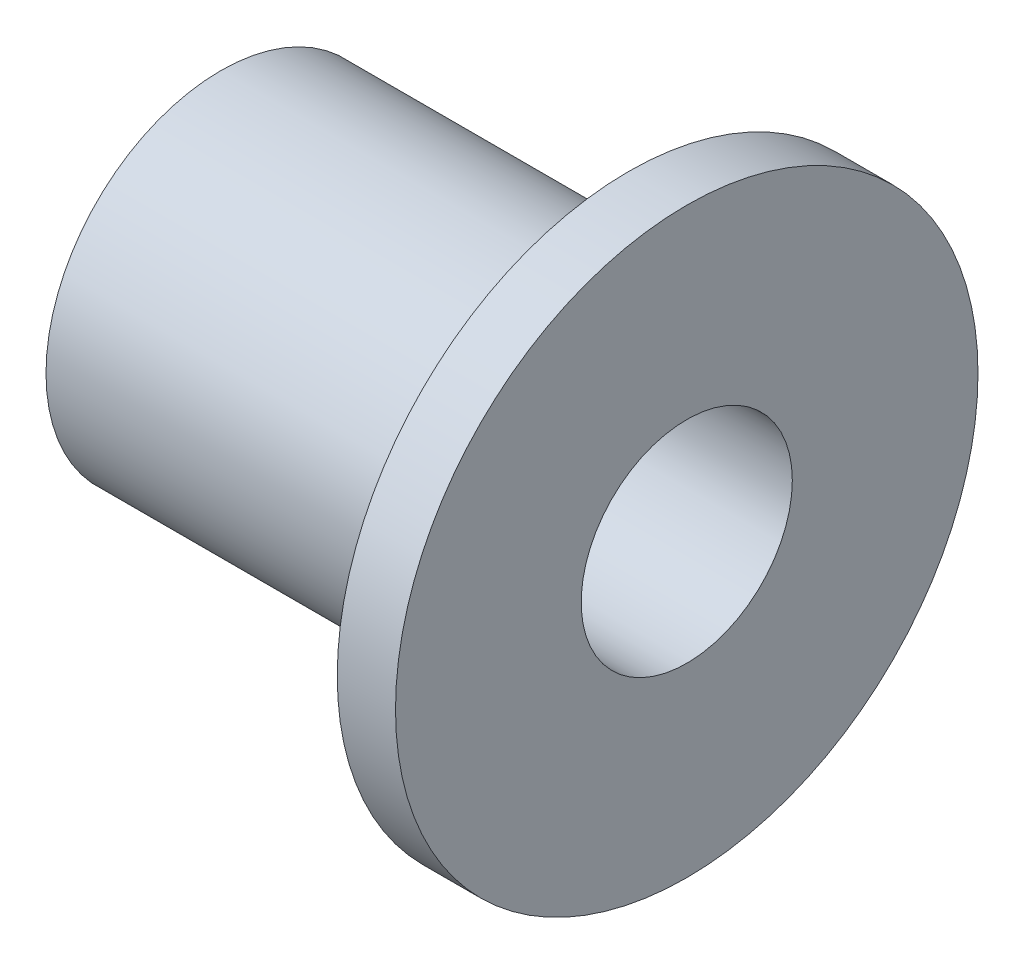
SolidWorks part; units mm, degrees
material "6061 Alloy"
ref_plane "Front Plane" through (0, 0, 0) normal (0, 0, 1) x (1, 0, 0)
ref_plane "Top Plane" through (0, 0, 0) normal (0, 1, 0) x (1, 0, 0)
ref_plane "Right Plane" through (0, 0, 0) normal (1, 0, 0) x (0, 0, -1)
sketch "Sketch1" plane through (0, 0, 0) normal (0, 0, 1) x (1, 0, 0)
  line L0 (0, 9.525) -> (22.225, 9.525)
  line L1 (22.225, 9.525) -> (22.225, 15.875)
  line L2 (22.225, 15.875) -> (25.4, 15.875)
  line L3 (25.4, 15.875) -> (25.4, 0)
  line L4 (25.4, 0) -> (0, 0)
  line L5 (0, 0) -> (0, 9.525)
  line L6 (0, 0) -> (39.6986, 0) construction
  dimension "D1" = 9.525
  dimension "D2" = 22.225
  dimension "D3" = 3.175
  dimension "D4" = 15.875
revolve "Revolve1" add sketch "Sketch1" angle 360 about L6
sketch "Sketch2" plane through (25.4, 0, 0) normal (1, 0, 0) x (0, 0, -1)
  point P0 (0, 0)
hole_wizard "1/2-20 Tapped Hole1" positions "3DSketch1" profile "Sketch3" tap size "1/2-20" standard "Ansi Inch" end condition through all
sketch3d "3DSketch1"
  point P0 (25.4, 0, 0)
sketch "Sketch3" plane through (25.4, 0, 0) normal (0, 1, 0) x (0, 0, -1)
  line L0 (0, 0) -> (0, 25.4)
  line L1 (0, 25.4) -> (5.7544, 25.4)
  line L2 (5.7544, 25.4) -> (5.7544, 0)
  line L5 (5.7544, 0) -> (0, 0)
  line L11 (0, -6.35) -> (0, 107.95) construction
  dimension "Thru Tap Drill Dia." = 11.5087
  dimension "Thru Tap Drill Depth" = 25.4
cosmetic thread "Hole Thread1" parameters "D2"=12.7
